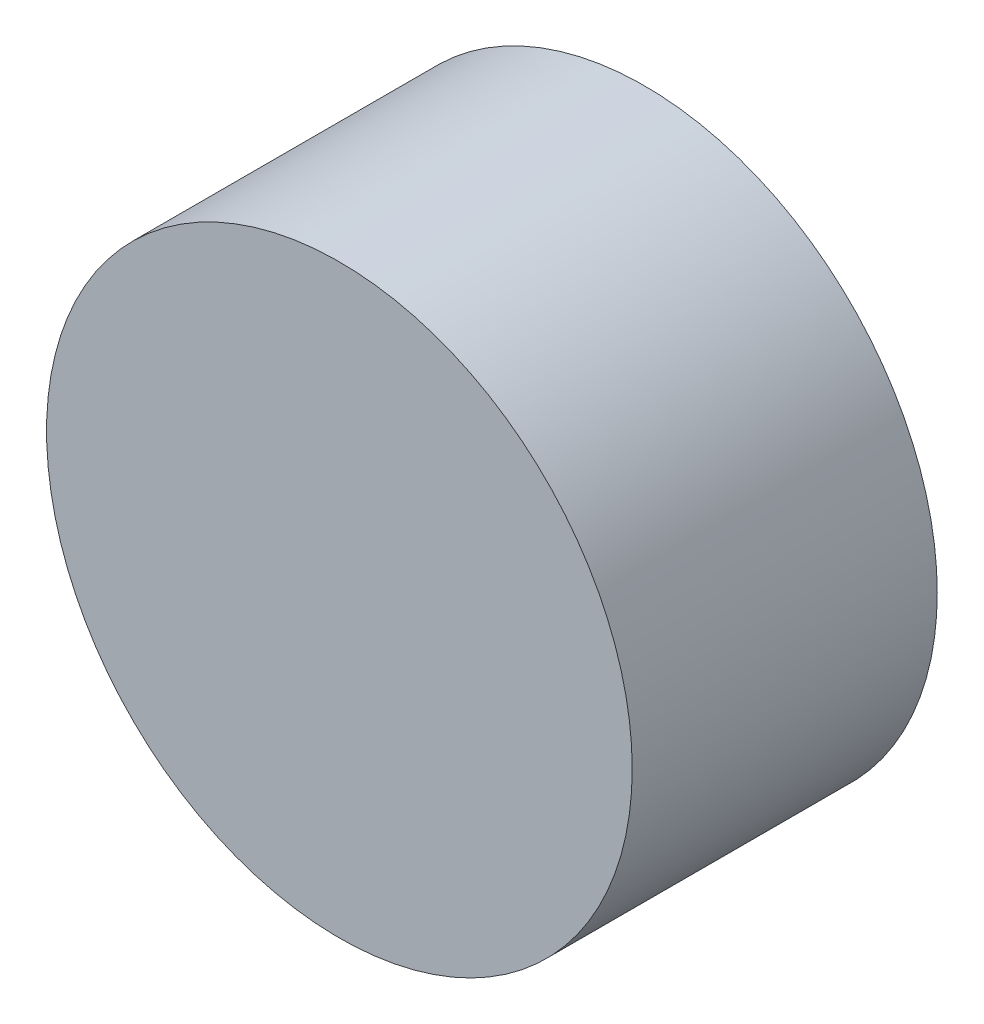
SolidWorks part; units mm, degrees
ref_plane "正面" through (0, 0, 0) normal (0, 0, 1) x (1, 0, 0)
ref_plane "平面" through (0, 0, 0) normal (0, 1, 0) x (1, 0, 0)
ref_plane "右側面" through (0, 0, 0) normal (1, 0, 0) x (0, 0, -1)
sketch "ｽｹｯﾁ1" plane through (0, 0, 0) normal (0, 0, 1) x (1, 0, 0)
  circle A0 centre (0, 0) radius 24
  dimension "D1" = 48
extrude "ﾎﾞｽ - 押し出し1" add sketch "ｽｹｯﾁ1" along normal blind 25
